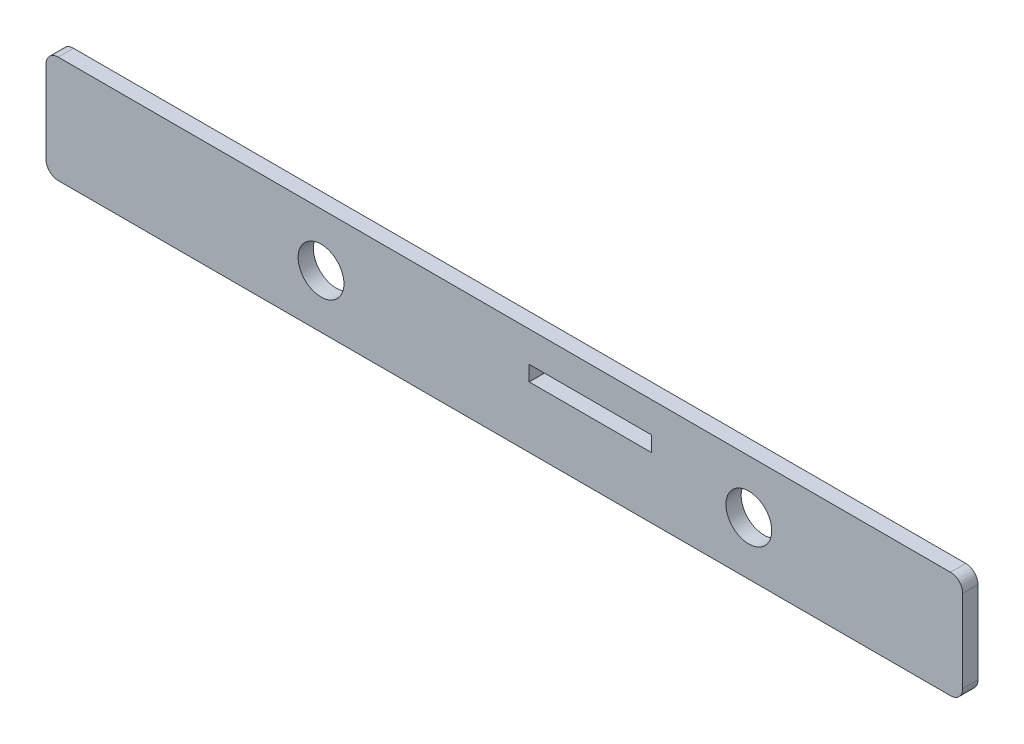
SolidWorks part; units mm, degrees
ref_plane "Front Plane" through (0, 0, 0) normal (0, 0, 1) x (1, 0, 0)
ref_plane "Top Plane" through (0, 0, 0) normal (0, 1, 0) x (1, 0, 0)
ref_plane "Right Plane" through (0, 0, 0) normal (1, 0, 0) x (0, 0, -1)
sketch "Sketch1" plane through (0, 0, 0) normal (0, 0, 1) x (1, 0, 0)
  line L1 (1104.9, -28.575) -> (1485.9, -28.575)
  line L2 (1104.9, -28.575) -> (1104.9, -73.025)
  line L3 (1104.9, -73.025) -> (1485.9, -73.025)
  line L4 (1485.9, -28.575) -> (1485.9, -73.025)
  circle A0 centre (1219.2, -50.8) radius 9.525
  circle A1 centre (1397, -50.8) radius 9.525
  point P11 (1104.9, -50.8)
  dimension "D4" = 19.05
  dimension "D6" = 1219.2
  dimension "D7" = 1397
  dimension "D1" = 44.45
  dimension "D2" = 1104.9
  dimension "D3" = 1485.9
  dimension "D5" = 73.025
extrude "Boss-Extrude1" add sketch "Sketch1" along normal blind 6.35
fillet "Fillet1" radius 5.08 4 edges at (1485.9, -73.025, 3.175) (1485.9, -28.575, 3.175) (1104.9, -73.025, 3.175) (1104.9, -28.575, 3.175)
sketch "Sketch2" plane through (0, 0, 6.35) normal (0, 0, 1) x (1, 0, 0)
  line L0 (1109.98, -73.025) -> (1480.82, -73.025) construction
  line L1 (1480.82, -28.575) -> (1109.98, -28.575) construction
  line L2 (1109.98, -73.025) -> (1480.82, -73.025)
  line L3 (1480.82, -28.575) -> (1109.98, -28.575)
  line L4 (1300.1625, -28.575) -> (1300.1625, -73.025)
  line L5 (1362.075, -28.575) -> (1362.075, -73.025)
  line L7 (1305.7188, -41.275) -> (1356.5187, -41.275)
  line L8 (1305.7188, -41.275) -> (1305.7188, -47.625)
  line L9 (1305.7188, -47.625) -> (1356.5187, -47.625)
  line L10 (1356.5187, -41.275) -> (1356.5187, -47.625)
  circle A0 centre (1397, -50.8) radius 9.525 construction
  circle A1 centre (1397, -50.8) radius 9.525
  dimension "D1" = 96.8375
  dimension "D2" = 34.925
  dimension "D3" = 61.9125
  dimension "D4" = 50.8
  dimension "D5" = 25.4
  dimension "D6" = 6.35
  dimension "D7" = 5.5562
extrude "Cut-Extrude1" cut sketch "Sketch2" against normal through all contours L10 L7 L8 L9 region at (1331.1188, -44.45, 6.35)
equation "\"D7@Sketch2\"=(\"D3@Sketch2\"-\"D4@Sketch2\")/2"
